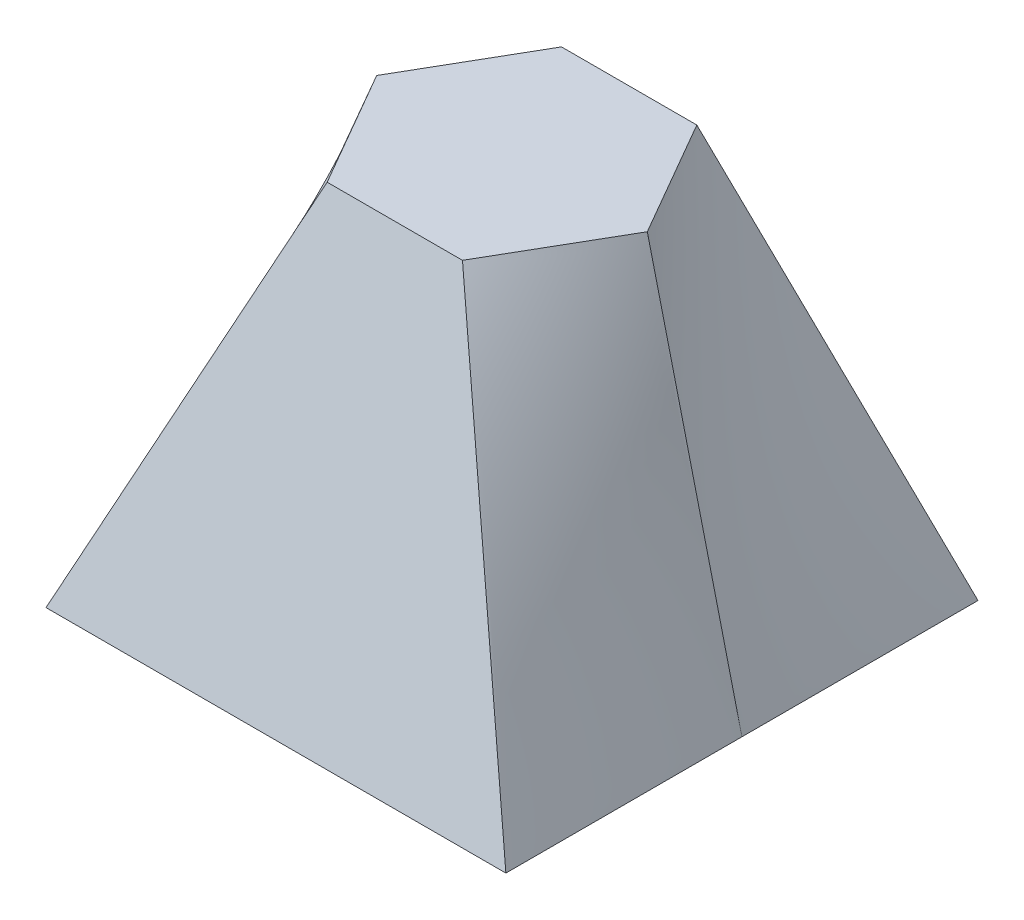
SolidWorks part; units mm, degrees
ref_plane "Front Plane" through (0, 0, 0) normal (0, 0, 1) x (1, 0, 0)
ref_plane "Top Plane" through (0, 0, 0) normal (0, 1, 0) x (1, 0, 0)
ref_plane "Right Plane" through (0, 0, 0) normal (1, 0, 0) x (0, 0, -1)
sketch "Sketch1" plane through (0, 0, 0) normal (0, 1, 0) x (1, 0, 0)
  line L0 (-44.9138, 0) -> (44.9138, 0) construction
  line L1 (-44.9138, -46.1106) -> (44.9138, -46.1106)
  line L2 (-44.9138, -46.1106) -> (-44.9138, 0)
  line L3 (-44.9138, 46.1106) -> (44.9138, 46.1106)
  line L4 (44.9138, -46.1106) -> (44.9138, 46.1106) construction
  line L5 (-44.9138, -46.1106) -> (44.9138, 46.1106) construction
  line L6 (-44.9138, 46.1106) -> (44.9138, -46.1106) construction
  line L7 (44.9138, 46.1106) -> (44.9138, 0)
  line L8 (44.9138, 0) -> (44.9138, -46.1106)
  line L9 (-44.9138, 0) -> (-44.9138, 46.1106)
  point P0 (0, 0)
  point P8 (-66.4971, 21.17)
ref_plane "Plane1" through (0, 76.2, 0) normal (0, 1, 0) x (1, 0, 0)
sketch "Sketch2" plane through (0, 76.2, 0) normal (0, 1, 0) x (1, 0, 0)
  line L0 (-44.9138, -46.1106) -> (44.9138, 46.1106) construction
  line L1 (26.43, 0) -> (13.215, 22.889)
  line L2 (13.215, 22.889) -> (-13.215, 22.889)
  line L3 (-13.215, 22.889) -> (-26.43, 0)
  line L4 (-26.43, 0) -> (-13.215, -22.889)
  line L5 (-13.215, -22.889) -> (13.215, -22.889)
  line L6 (13.215, -22.889) -> (26.43, 0)
  circle A0 centre (0, 0) radius 22.889 construction
loft "Loft2" add profiles "Sketch1", "Sketch2"
